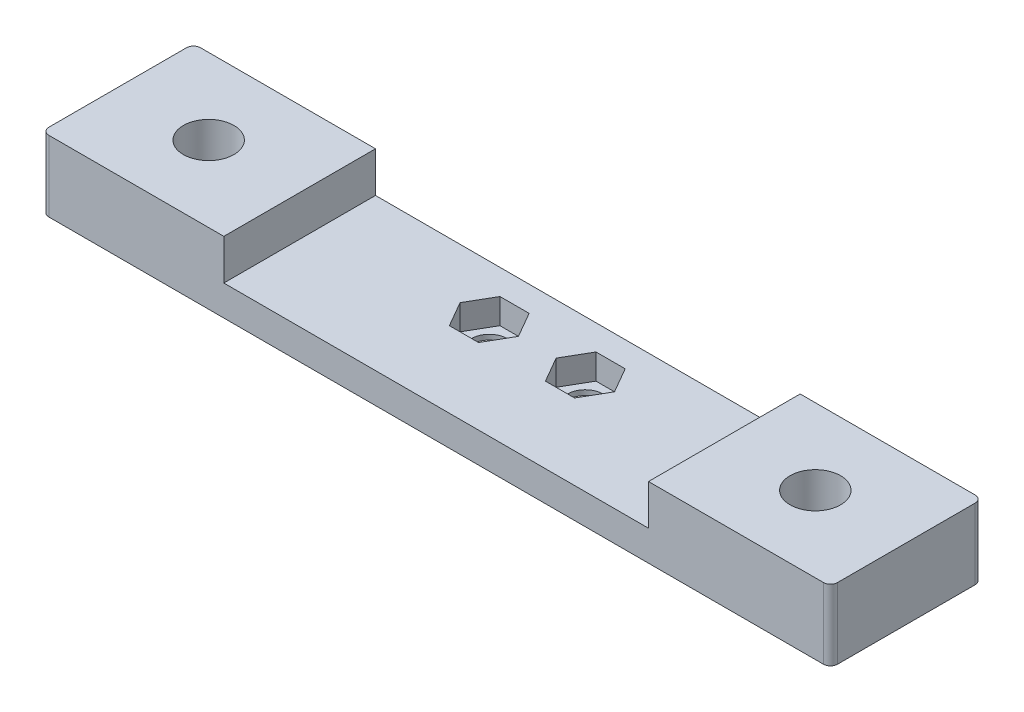
SolidWorks part; units mm, degrees
ref_plane "Front Plane" through (0, 0, 0) normal (0, 0, 1) x (1, 0, 0)
ref_plane "Top Plane" through (0, 0, 0) normal (0, 1, 0) x (1, 0, 0)
ref_plane "Right Plane" through (0, 0, 0) normal (1, 0, 0) x (0, 0, -1)
sketch "Sketch1" plane through (0, 0, 0) normal (0, 1, 0) x (1, 0, 0)
  line L0 (9, 7.5) -> (69, 7.5) construction
  line L1 (0, 0) -> (78, 0)
  line L2 (0, 0) -> (0, 15)
  line L3 (0, 15) -> (78, 15)
  line L4 (78, 0) -> (78, 15)
  line L5 (34.25, 10) -> (43.75, 10) construction
  line L7 (32.8066, 12.5) -> (31.3632, 10)
  line L8 (31.3632, 10) -> (32.8066, 7.5)
  line L9 (32.8066, 7.5) -> (35.6934, 7.5)
  line L10 (35.6934, 7.5) -> (37.1368, 10)
  line L11 (37.1368, 10) -> (35.6934, 12.5)
  line L12 (35.6934, 12.5) -> (32.8066, 12.5)
  line L13 (45.1934, 12.5) -> (42.3066, 12.5)
  line L14 (42.3066, 12.5) -> (40.8632, 10)
  line L15 (40.8632, 10) -> (42.3066, 7.5)
  line L16 (42.3066, 7.5) -> (45.1934, 7.5)
  line L17 (45.1934, 7.5) -> (46.6368, 10)
  line L18 (46.6368, 10) -> (45.1934, 12.5)
  circle A0 centre (9, 7.5) radius 2.5
  circle A1 centre (69, 7.5) radius 2.5
  circle A2 centre (34.25, 10) radius 1.75
  circle A3 centre (43.75, 10) radius 1.75
  circle A4 centre (34.25, 10) radius 2.5 construction
  circle A5 centre (43.75, 10) radius 2.5 construction
  point P9 (39, 7.5)
  point P10 (39, 0)
  point P13 (0, 7.5)
  point P16 (39, 10)
  point P17 (39, 15)
  dimension "D4" = 5
  dimension "D6" = 3.5
  dimension "D1" = 15
  dimension "D2" = 9
  dimension "D3" = 60
  dimension "D5" = 9.5
  dimension "D7" = 5
  dimension "D8" = 10
extrude "Boss-Extrude1" add sketch "Sketch1" along normal blind 3 contours L1 L4 L3 L2 A1 A0 L18 L17 L16 L15 L14 L13 L12 L11 L10 L9 L8 L7 region at (39, 0, -7.4005)
extrude "Boss-Extrude2" add sketch "Sketch1<3>" along normal blind 0.5 contours L11 L12 L7 L8 L9 L10 A2 | L17 L18 L13 L14 L15 L16 A3 region at (34.25, 0, -12.4236) region at (45.8489, 0, -11.2118)
sketch "Sketch1<3>" plane through (0, 0, 0) normal (0, 1, 0) x (1, 0, 0) same geometry as "Sketch1"
fillet "Fillet1" radius 0.7 4 edges at (78, 1.5, -15) (78, 1.5, 0) (0, 1.5, 0) (0, 1.5, -15)
sketch "Sketch2" plane through (0, 0, 0) normal (0, -1, 0) x (-1, 0, 0)
  line L0 (-60, 0) -> (-60, 15)
  line L1 (-0.7, 0) -> (-77.3, 0) construction
  line L2 (-0.7, 15) -> (-77.3, 15) construction
  line L3 (-18, 0) -> (-18, 15)
  line L4 (-18, 7.5) -> (0, 7.5) construction
  line L5 (0, 0.7) -> (0, 14.3) construction
  line L6 (-60, 7.5) -> (-78, 7.5) construction
  line L7 (-78, 0.7) -> (-78, 14.3) construction
  circle A0 centre (-69, 7.5) radius 2.5 construction
  circle A1 centre (-9, 7.5) radius 2.5 construction
  point P16 (-69, 7.5)
  point P21 (-9, 7.5)
  circle M1 centre (-69, 7.5) radius 2.5
  circle M2 centre (-9, 7.5) radius 2.5
  line M3 (-0.7, 15) -> (-77.3, 15)
  arc M4 (-77.3, 15) -> (-78, 14.3) centre (-77.3, 14.3) ccw
  line M5 (-78, 14.3) -> (-78, 0.7)
  arc M6 (-78, 0.7) -> (-77.3, 0) centre (-77.3, 0.7) ccw
  line M7 (-77.3, 0) -> (-0.7, 0)
  arc M8 (-0.7, 0) -> (0, 0.7) centre (-0.7, 0.7) ccw
  line M9 (0, 0.7) -> (0, 14.3)
  arc M10 (0, 14.3) -> (-0.7, 15) centre (-0.7, 14.3) ccw
extrude "Boss-Extrude3" add sketch "Sketch2" against normal blind 7 contours L0 M7 M3 M4 M5 M6 M1 | L3 M7 M8 M9 M10 M3 M2 region at (68.65, 0, -0.2343) region at (17.7657, 0, -7.5)
